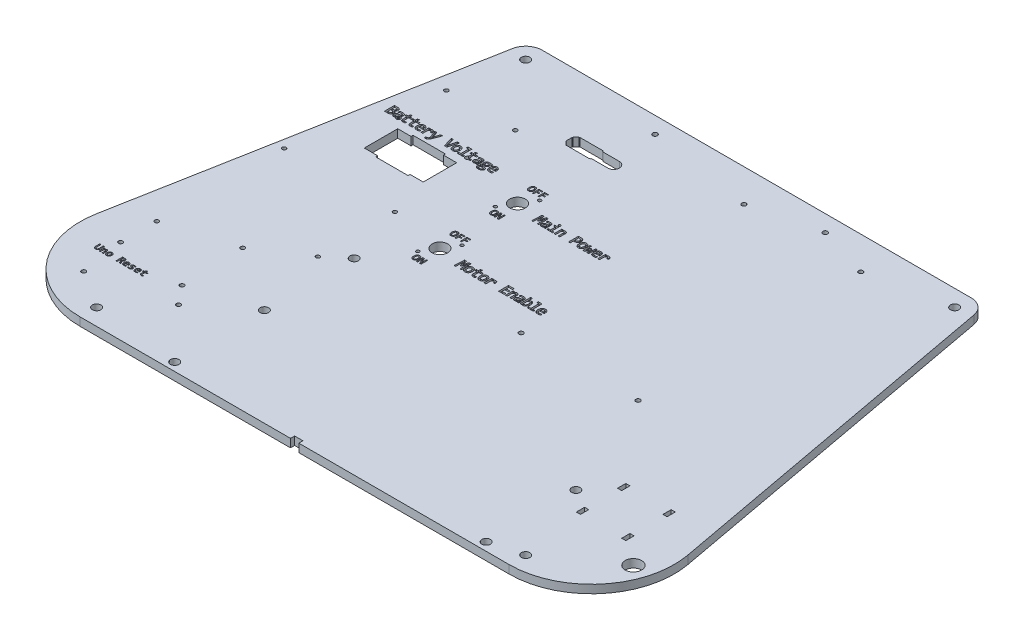
SolidWorks part; units mm, degrees
material "Acrylic (Medium-high impact)"
ref_plane "Front Plane" through (0, 0, 0) normal (0, 0, 1) x (1, 0, 0)
ref_plane "Top Plane" through (0, 0, 0) normal (0, 1, 0) x (1, 0, 0)
ref_plane "Right Plane" through (0, 0, 0) normal (1, 0, 0) x (0, 0, -1)
sketch "Sketch1" plane through (0, 0, 0) normal (0, 1, 0) x (1, 0, 0)
  line L0 (-165.1, -177.8) -> (-3.175, -177.8)
  line L1 (165.1, -165.1) -> (-165.1, -165.1) construction
  line L2 (165.1, -165.1) -> (165.1, 165.1) construction
  line L3 (165.1, 165.1) -> (-165.1, 165.1) construction
  line L4 (-165.1, -165.1) -> (-165.1, 165.1) construction
  line L5 (165.1, -165.1) -> (-165.1, 165.1) construction
  line L6 (165.1, 165.1) -> (-165.1, -165.1) construction
  line L7 (-165.1, 177.8) -> (165.1, 177.8)
  line L8 (-227.5416, -102.7545) -> (-177.5883, 167.4091)
  line L9 (177.5883, 167.4091) -> (227.5416, -102.7545)
  line L10 (0, 0) -> (0, 177.8) construction
  line L11 (0, 0) -> (0, -177.8) construction
  line L12 (-65.5, 165.1) -> (65.5, 165.1) construction
  line L13 (-3.175, -177.8) -> (-3.175, -174.625)
  line L14 (-3.175, -174.625) -> (3.175, -174.625)
  line L15 (3.175, -174.625) -> (3.175, -177.8)
  line L16 (3.175, -177.8) -> (165.1, -177.8)
  circle A0 centre (-165.1, 165.1) radius 3.2639
  circle A1 centre (165.1, 165.1) radius 3.2639
  circle A2 centre (165.1, -165.1) radius 3.2639
  circle A3 centre (-165.1, -165.1) radius 3.2639
  arc A4 (-165.1, 177.8) -> (-177.5883, 167.4091) centre (-165.1, 165.1) ccw
  arc A5 (165.1, 177.8) -> (177.5883, 167.4091) centre (165.1, 165.1) cw
  arc A6 (-227.5416, -102.7545) -> (-165.1, -177.8) centre (-165.1, -114.3) ccw
  arc A7 (165.1, -177.8) -> (227.5416, -102.7545) centre (165.1, -114.3) ccw
  circle A8 centre (-65.5, 165.1) radius 1.8288
  circle A9 centre (65.5, 165.1) radius 1.8288
  point P0 (0, 0)
  point P1 (165.1, -114.3)
  point P27 (0, 165.1)
  point P32 (0, -174.625)
  dimension "D2" = 6.5278
  dimension "D6" = 3.6576
  dimension "D1" = 330.2
  dimension "D3" = 12.7
  dimension "D4" = 12.7
  dimension "D5" = 63.5
  dimension "D7" = 131
  dimension "D8" = 165.1
  dimension "D9" = 3.175
  dimension "D10" = 6.35
extrude "Boss-Extrude1" add sketch "Sketch1" along normal blind 6.35
sketch "Sketch2" plane through (0, 6.35, 0) normal (0, 1, 0) x (1, 0, 0)
  line L0 (-95.3811, 131.405) -> (-92.6311, 134.155)
  line L2 (-95.3811, 134.155) -> (-73.8811, 134.155)
  line L3 (-95.3811, 134.155) -> (-95.3811, 123.655)
  line L4 (-73.8811, 133.35) -> (-61.1811, 133.35)
  line L5 (-61.1811, 124.46) -> (-73.8811, 124.46)
  line L6 (165.1, 177.8) -> (-165.1, 177.8) construction
  line L7 (-95.3811, 123.655) -> (-73.8811, 123.655)
  line L8 (-73.8811, 134.155) -> (-73.8811, 123.655)
  line L9 (-92.6311, 123.655) -> (-95.3811, 126.405)
  line L10 (-61.1811, 128.905) -> (-95.3811, 128.905) construction
  arc A2 (-61.1811, 133.35) -> (-61.1811, 124.46) centre (-61.1811, 128.905) cw
  dimension "D1" = 8.89
  dimension "D2" = 12.7
  dimension "D3" = 44.45
  dimension "D4" = 61.1811
  dimension "D5" = 21.5
  dimension "D6" = 10.5
  dimension "D7" = 45
  dimension "D8" = 45
  dimension "D9" = 5
extrude "Cut-Extrude1" cut sketch "Sketch2" against normal through all contours A2 L4 L8 L5 | L10 L8 L2 L0 L3 | L8 L10 L3 L9 L7 region at (-84.2903, 6.35, -131.4708) region at (-84.2903, 6.35, -126.3392) region at (-73.688, 6.35, -131.1275)
sketch "Sketch3" plane through (0, 6.35, -6.35) normal (0, -1, 0) x (1, 0, 0)
  line L0 (165.1, -171.45) -> (-165.1, -171.45) construction
  line L1 (105.325, -146.2786) -> (105.325, 25.1714) construction
  line L2 (105.325, -146.2786) -> (15.325, -146.2786) construction
  line L3 (15.325, -146.2786) -> (15.325, 25.1714) construction
  line L4 (105.325, 25.1714) -> (15.325, 25.1714) construction
  line L5 (105.325, -146.2786) -> (15.325, 25.1714) construction
  line L6 (15.325, -146.2786) -> (105.325, 25.1714) construction
  circle A0 centre (15.325, -146.2786) radius 1.7
  circle A1 centre (15.325, 25.1714) radius 1.7
  circle A2 centre (105.325, 25.1714) radius 1.7
  circle A3 centre (105.325, -146.2786) radius 1.7
  point P0 (60.325, -60.5536)
  dimension "D1" = 3.4
  dimension "D2" = 90
  dimension "D3" = 171.45
  dimension "D4" = 110.8964
  dimension "D5" = 104.775
extrude "Cut-Extrude6" cut sketch "Sketch3" along normal through all
sketch "Sketch4" plane through (0, 6.35, 0) normal (0, 1, 0) x (1, 0, 0)
  line L0 (165.1, 177.8) -> (-165.1, 177.8) construction
  line L1 (-168.2882, 69.85) -> (-158.0647, 69.85)
  line L2 (-168.2882, 69.85) -> (-168.2882, 44.1198)
  line L3 (-168.2882, 44.1198) -> (-158.0647, 44.1198)
  line L4 (-122.9492, 69.85) -> (-122.9492, 44.1198)
  line L5 (-145.6187, 71.374) -> (-145.6187, 56.9849) construction
  line L6 (-133.1727, 44.1198) -> (-122.9492, 44.1198)
  line L7 (-158.0647, 69.85) -> (-158.0647, 71.374)
  line L8 (-158.0647, 71.374) -> (-133.1727, 71.374)
  line L9 (-133.1727, 69.85) -> (-133.1727, 71.374)
  line L10 (-168.2882, 56.9849) -> (-122.9492, 56.9849) construction
  line L11 (-133.1727, 44.1198) -> (-133.1727, 42.5958)
  line L12 (-158.0647, 42.5958) -> (-133.1727, 42.5958)
  line L13 (-158.0647, 44.1198) -> (-158.0647, 42.5958)
  line L14 (-133.1727, 69.85) -> (-122.9492, 69.85)
  circle A0 centre (-72.338, 66.0911) radius 6
  circle A1 centre (-72.338, 6.3597) radius 6
  circle A2 centre (-65.8737, 76.6321) radius 1.25
  circle A3 centre (-78.8023, 55.5501) radius 1.25
  circle A4 centre (-65.8737, 16.9007) radius 1.25
  circle A5 centre (-78.8023, -4.1813) radius 1.25
  dimension "D1" = 12
  dimension "D10" = 2.5
  dimension "D2" = 45.339
  dimension "D3" = 25.7302
  dimension "D4" = 72.338
  dimension "D5" = 6.3597
  dimension "D6" = 66.0911
  dimension "D7" = 72.338
  dimension "D8" = 107.95
  dimension "D9" = 122.9492
  dimension "D11" = 10.541
  dimension "D12" = 6.4643
  dimension "D13" = 10.541
  dimension "D14" = 6.4643
  dimension "D15" = 10.541
  dimension "D16" = 6.4643
  dimension "D17" = 10.541
  dimension "D18" = 6.4643
  dimension "D19" = 24.892
  dimension "D20" = 1.524
extrude "Cut-Extrude7" cut sketch "Sketch4" against normal through all
sketch "Sketch5" plane through (0, 6.35, 0) normal (0, 1, 0) x (1, 0, 0)
  line L0 (-72.338, 60.0911) -> (16.4248, 60.0911) construction
  line L1 (-72.338, 0.3597) -> (21.2307, 0.3597) construction
  line L2 (-185.7752, 76.45) -> (-66.0177, 76.45) construction
  line L3 (165.1, 177.8) -> (-165.1, 177.8) construction
  line L4 (-78.688, 78.7911) -> (-59.7976, 78.7911) construction
  line L5 (-77.418, 48.3111) -> (-57.2576, 48.3111) construction
  line L6 (-78.688, 19.0597) -> (-61.9228, 19.0597) construction
  line L7 (-77.418, -11.4203) -> (-57.2576, -11.4203) construction
  circle A0 centre (-72.338, 66.0911) radius 6 construction
  circle A1 centre (-72.338, 6.3597) radius 6 construction
  text T0 "   Main Power" font "Consolas" height 7.62
  text T1 "   Motor Enable" font "Consolas" height 7.62
  text T2 "Battery Voltage" font "Consolas" height 7.62
  text T3 "OFF" font "Consolas" height 5.08
  text T4 "OFF\r\n" font "Consolas" height 5.08
  text T5 "ON" font "Consolas" height 5.08
  text T6 "ON" font "Consolas" height 5.08
  dimension "D1" = 101.35
  dimension "D2" = 6.35
  dimension "D3" = 12.7
  dimension "D4" = 12.7
  dimension "D5" = 6.35
  dimension "D6" = 5.08
  dimension "D7" = 17.78
  dimension "D8" = 5.08
  dimension "D9" = 17.78
extrude "Cut-Extrude8" cut sketch "Sketch5" against normal blind 1.5875
sketch "Sketch6" plane through (0, 6.35, 0) normal (0, 1, 0) x (1, 0, 0)
  line L0 (159.094, -113.7425) -> (190.844, -113.7425) construction
  line L1 (187.9752, -69.2925) -> (161.9752, -69.2925) construction
  line L2 (187.9752, -142.2925) -> (187.9752, -69.2925) construction
  line L3 (165.9752, -146.2925) -> (183.9752, -146.2925) construction
  line L4 (159.094, -81.9925) -> (190.844, -81.9925) construction
  line L5 (190.844, -78.8175) -> (194.019, -78.8175)
  line L6 (190.844, -78.8175) -> (190.844, -85.1675)
  line L7 (190.844, -85.1675) -> (194.019, -85.1675)
  line L8 (194.019, -78.8175) -> (194.019, -85.1675)
  line L9 (155.919, -78.8175) -> (159.094, -78.8175)
  line L10 (155.919, -78.8175) -> (155.919, -85.1675)
  line L11 (155.919, -85.1675) -> (159.094, -85.1675)
  line L12 (159.094, -78.8175) -> (159.094, -85.1675)
  line L13 (155.919, -110.5675) -> (159.094, -110.5675)
  line L14 (155.919, -110.5675) -> (155.919, -116.9175)
  line L15 (155.919, -116.9175) -> (159.094, -116.9175)
  line L16 (159.094, -110.5675) -> (159.094, -116.9175)
  line L17 (190.844, -110.5675) -> (194.019, -110.5675)
  line L18 (190.844, -110.5675) -> (190.844, -116.9175)
  line L19 (190.844, -116.9175) -> (194.019, -116.9175)
  line L20 (194.019, -110.5675) -> (194.019, -116.9175)
  line L21 (174.9667, -57.7925) -> (174.9752, -146.2925) construction
  line L22 (169.1667, -57.7925) -> (180.7667, -57.7925) construction
  circle A0 centre (-175.0794, 114.0576) radius 1.5875
  circle A1 centre (-122.0794, 114.0576) radius 1.5875
  circle A2 centre (-122.0794, 77.2576) radius 1.5875
  circle A3 centre (-175.0794, 77.2576) radius 1.5875
  circle A4 centre (-198.9217, 13.0738) radius 1.4732
  circle A5 centre (-113.922, 13.3085) radius 1.4732
  circle A6 centre (-113.7577, -46.1913) radius 1.4793
  circle A7 centre (-199.3418, -84.5435) radius 1.6
  circle A8 centre (-199.3418, -112.4435) radius 1.6
  circle A9 centre (-146.9418, -117.5435) radius 1.6
  circle A10 centre (-148.5418, -69.2435) radius 1.6
  circle A11 centre (-194.0161, -146.1037) radius 1.651
  circle A12 centre (-135.2786, -131.8162) radius 1.651
  circle A13 centre (-98.6512, -33.3375) radius 3.2639
  circle A14 centre (-98.6512, -102.3938) radius 3.2639
  circle A15 centre (-98.6512, -171.45) radius 3.2639
  circle A16 centre (141.0613, -171.45) radius 3.2639
  circle A17 centre (141.0613, -102.3938) radius 3.2639
  circle A18 centre (213.3752, -130.4429) radius 6.35
  point P78 (174.969, -81.9925)
  point P83 (174.969, -113.7425)
  dimension "D1" = 12.7
  dimension "D9" = 6.5278
  dimension "D2" = 25.4
  dimension "D3" = 15.8496
  dimension "D4" = 6.35
  dimension "D5" = 3.175
  dimension "D6" = 31.75
  dimension "D7" = 31.75
  dimension "D8" = 12.7
extrude "Cut-Extrude9" cut sketch "Sketch6" against normal through all
fillet "Fillet1" radius 1 6 edges at (-73.8811, 3.175, -134.155) (-73.8811, 3.175, -123.655) (-92.6311, 3.175, -123.655) (-92.6311, 3.175, -134.155) (-95.3811, 3.175, -126.405) (-95.3811, 3.175, -131.405)
sketch "Sketch7" plane through (0, 6.35, 0) normal (0, 1, 0) x (1, 0, 0)
  line L0 (-173.9418, -79.4035) -> (-152.8229, -79.4035) construction
  circle A0 centre (-148.5418, -69.2435) radius 1.6 construction
  text T0 "Uno Reset" font "Consolas" height 5.08
  dimension "D1" = 25.4
  dimension "D2" = 10.16
extrude "Cut-Extrude10" cut sketch "Sketch7" against normal blind 1.5875
